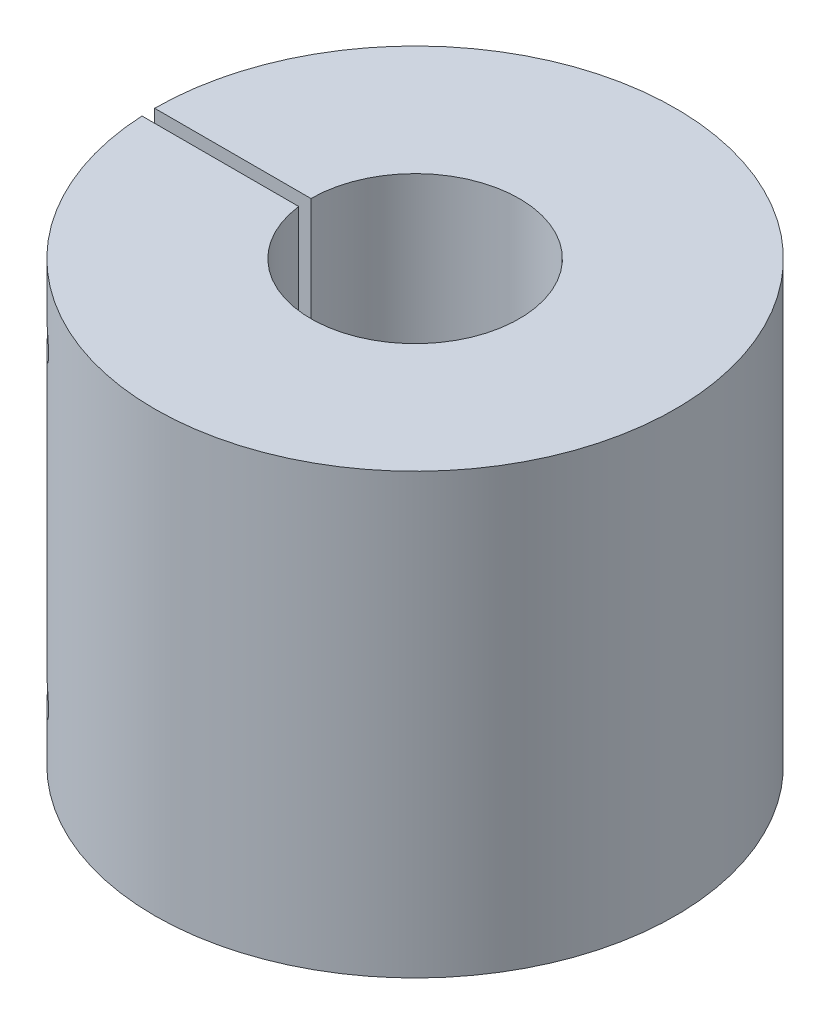
SolidWorks part; units mm, degrees
ref_plane "Front Plane" through (0, 0, 0) normal (0, 0, 1) x (1, 0, 0)
ref_plane "Top Plane" through (0, 0, 0) normal (0, 1, 0) x (1, 0, 0)
ref_plane "Right Plane" through (0, 0, 0) normal (1, 0, 0) x (0, 0, -1)
sketch "Sketch1" plane through (0, 0, 0) normal (0, 1, 0) x (1, 0, 0)
  circle A0 centre (0, 0) radius 25.4
  dimension "D1" = 50.8
extrude "Boss-Extrude1" add sketch "Sketch1" along normal blind 42.799
sketch "Sketch2" plane through (0, 42.799, 0) normal (0, 1, 0) x (1, 0, 0)
  line L0 (-10.16, 0) -> (-25.4, 0)
  line L1 (-10.0803, -1.27) -> (-25.3682, -1.27)
  circle A0 centre (0, 0) radius 10.16 construction
  circle A1 centre (0, 0) radius 25.4 construction
  arc A2 (-25.4, 0) -> (-25.3682, -1.27) centre (0, 0) ccw
  arc A3 (-10.16, 0) -> (-10.0803, -1.27) centre (0, 0) cw
  point P9 (-15.24, 0)
  point P10 (-20.32, 0)
  dimension "D2" = 20.32
  dimension "D1" = 1.27
  dimension "D3" = 15.24
  dimension "D4" = 5.08
  dimension "D5" = 5.08
extrude "Cut-Extrude1" cut sketch "Sketch2" against normal through all
ref_plane "Plane1" through (0, 0, -25.4) normal (0, 0, 1) x (1, 0, 0)
ref_axis "Axis2" through (-25.4, -42.2388, 0) along (0, 1, 0)
sketch "Sketch3" plane through (0, 0, -25.4) normal (0, 0, 1) x (1, 0, 0)
  line L0 (-17.78, 0) -> (-17.78, 42.799) construction
  line L1 (-25.4, -42.2388) -> (-25.4, 79.618) construction
  line L2 (19.027, 0) -> (-17.78, 0) construction
  circle A0 centre (-17.78, 36.449) radius 1.651
  circle A1 centre (-17.78, 6.35) radius 1.651
  point P8 (0, 0)
  point P9 (-18.3705, 0.4172)
  point P10 (-17.78, -1.0661)
  point P11 (-17.78, 40.64)
  dimension "D4" = 3.302
  dimension "D1" = 7.62
  dimension "D2" = 6.35
  dimension "D3" = 6.35
  dimension "D5" = 42.799
extrude "Cut-Extrude2" cut sketch "Sketch3" along normal through all both and the other way through all
